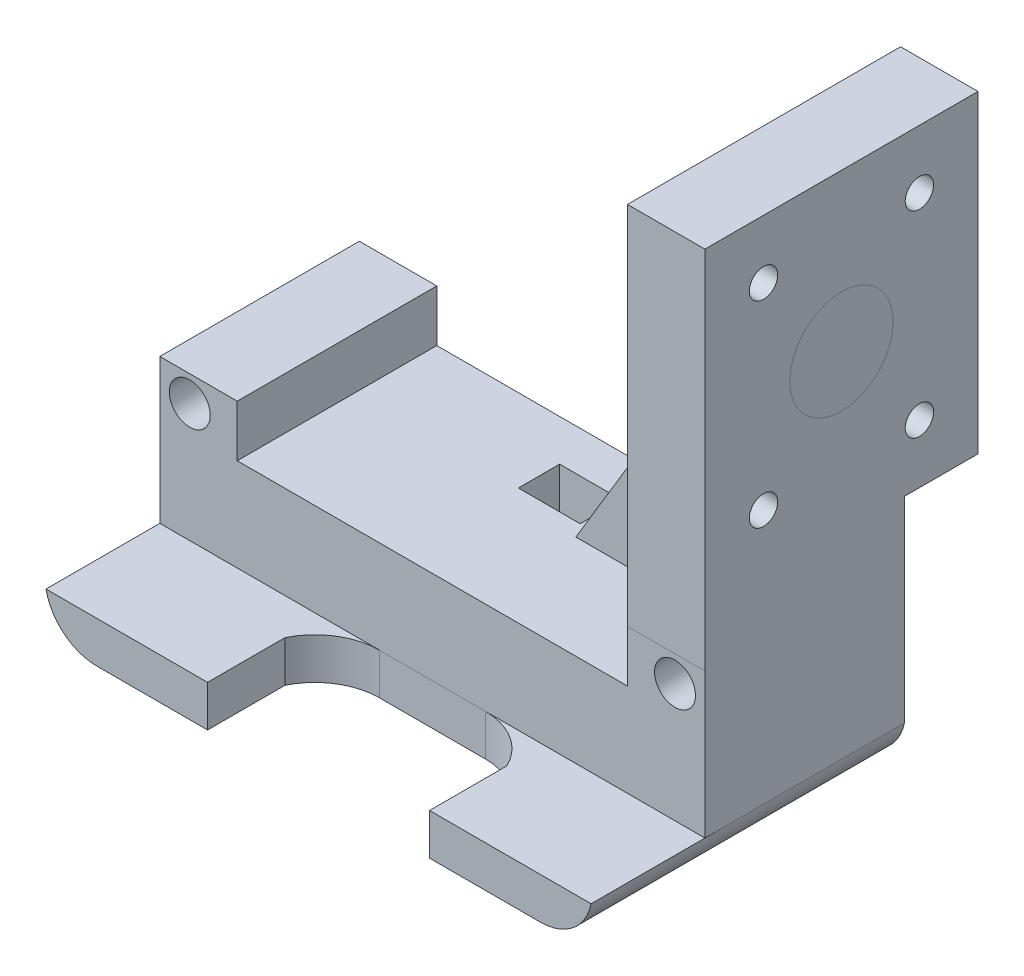
SolidWorks part; units mm, degrees
material "Custom Plastic"
ref_plane "Front Plane" through (0, 0, 0) normal (0, 0, 1) x (1, 0, 0)
ref_plane "Top Plane" through (0, 0, 0) normal (0, 1, 0) x (1, 0, 0)
ref_plane "Right Plane" through (0, 0, 0) normal (1, 0, 0) x (0, 0, -1)
sketch "Sketch2" plane through (0, 0, 0) normal (0, 1, 0) x (1, 0, 0)
  line L1 (-45, -15) -> (45, -15)
  line L2 (-45, -15) -> (-45, 15)
  line L3 (-45, 15) -> (45, 15)
  line L4 (45, -15) -> (45, 15)
  dimension "D1" = 90
  dimension "D2" = 30
  dimension "D3" = 15
  dimension "D4" = 45
extrude "Boss-Extrude1" add sketch "Sketch2" along normal blind 184.15
shell "Shell1" thickness 8 removed face at (0, 92.075, 15) outward yes
fillet "Fillet1" radius 10 8 edges at (53, 192.15, -4) (-53, 192.15, -4) (53, -8, -4) (-53, -8, -4) (45, 184.15, 0) (-45, 184.15, 0) (-45, 0, 0) (45, 0, 0)
sketch "Sketch3" plane through (0, -8, 0) normal (0, -1, 0) x (1, 0, 0)
  line L4 (-43, 15) -> (43, 15) construction
  line L5 (-21.5, 15) -> (21.5, 15)
  line L6 (-10.2526, -7.0461) -> (10.2526, -7.0461)
  line L7 (-21.5, 0) -> (-21.5, 15)
  line L8 (0, 36.7224) -> (0, -40.113) construction
  line L9 (21.5, 0) -> (21.5, 15)
  arc A0 (-10.2526, -7.0461) -> (-21.5, 0) centre (-10.2526, 5.4539) cw
  arc A1 (10.2526, -7.0461) -> (21.5, 0) centre (10.2526, 5.4539) ccw
  point P11 (0, -7.0461)
  dimension "D1" = 20.5051
  dimension "D2" = 43
  dimension "D4" = 12.5
  dimension "D5" = 15
extrude "Cut-Extrude1" cut sketch "Sketch3" against normal blind 15
sketch "Sketch16" plane through (0, 0, -23) normal (0, 0, -1) x (-1, 0, 0)
  line L0 (-53, 182.15) -> (-53, 2)
  line L1 (-43, -8) -> (43, -8)
  line L2 (53, 2) -> (53, 182.15)
  line L3 (43, 192.15) -> (-43, 192.15)
  arc A0 (-53, 2) -> (-43, -8) centre (-43, 2) ccw
  arc A1 (43, -8) -> (53, 2) centre (43, 2) ccw
  arc A2 (53, 182.15) -> (43, 192.15) centre (43, 182.15) ccw
  arc A3 (-43, 192.15) -> (-53, 182.15) centre (-43, 182.15) ccw
extrude "Boss-Extrude3" add sketch "Sketch16" along normal blind 12.7
sketch "Sketch19" plane through (53, 0, 0) normal (1, 0, 0) x (0, 0, -1)
  line L1 (-15, 192.15) -> (35.7, 192.15)
  line L2 (-15, 192.15) -> (-15, 2)
  line L3 (-15, 2) -> (35.7, 2)
  line L4 (35.7, 192.15) -> (35.7, 2)
extrude "Cut-Extrude3" cut sketch "Sketch19" against normal blind 160
sketch "Sketch20" plane through (0, 0, -15) normal (0, 0, 1) x (1, 0, 0)
  line L4 (41, 2) -> (-41, 2)
  line L5 (-35, 0) -> (35, 0)
  line L6 (41, 2) -> (-41, 2)
  line L7 (-35, 0) -> (35, 0)
  arc A4 (-41, 2) -> (-35, 0) centre (-35, 10) ccw
  arc A5 (35, 0) -> (41, 2) centre (35, 10) ccw
  arc A6 (-41, 2) -> (-35, 0) centre (-35, 10) ccw
  arc A7 (35, 0) -> (41, 2) centre (35, 10) ccw
  dimension "D1" = 0
extrude "Cut-Extrude4" cut sketch "Sketch20" against normal through all
sketch "Sketch21" plane through (21.5, 0, 0) normal (-1, 0, 0) x (0, 0, 1)
  line L1 (15, 0) -> (-35.7, 0)
  line L2 (15, 0) -> (15, 2)
  line L3 (15, 2) -> (-35.7, 2)
  line L4 (-35.7, 0) -> (-35.7, 2)
extrude "Cut-Extrude5" cut sketch "Sketch21" against normal through all and the other way through all
sketch "Sketch22" plane through (0, 0, 0) normal (0, 1, 0) x (1, 0, 0)
  line L0 (52.798, -15) -> (52.798, 35.7) construction
  line L1 (-52.798, 35.7) -> (52.798, 35.7)
  line L2 (-52.798, 35.7) -> (-52.798, 7.0461)
  line L3 (-52.798, 7.0461) -> (52.798, 7.0461)
  line L4 (52.798, 35.7) -> (52.798, 7.0461)
  dimension "D1" = 28.6539
extrude "Boss-Extrude4" add sketch "Sketch22" along normal blind 18
sketch "Sketch25" plane through (0, 18, 0) normal (0, 1, 0) x (1, 0, 0)
  line L0 (52.798, 35.7) -> (-52.798, 35.7) construction
  line L1 (-6, 35.7) -> (6, 35.7)
  line L2 (-6, 35.7) -> (-6, 29.7)
  line L3 (-6, 29.7) -> (6, 29.7)
  line L4 (6, 35.7) -> (6, 29.7)
  dimension "D1" = 6
  dimension "D2" = 6
  dimension "D3" = 12
extrude "Cut-Extrude7" cut sketch "Sketch25" against normal through all
sketch "Sketch26" plane through (0, 0, -35.7) normal (0, 0, -1) x (-1, 0, 0)
  line L8 (6, 18) -> (6, -8)
  line L9 (6, -8) -> (43, -8)
  line L10 (52.798, 0) -> (52.798, 18)
  line L11 (52.798, 18) -> (6, 18)
  line L12 (6, 18) -> (6, -8)
  line L13 (6, -8) -> (43, -8)
  line L14 (52.798, 0) -> (52.798, 18)
  line L15 (52.798, 18) -> (6, 18)
  line L20 (-6, -8) -> (-6, 18)
  line L21 (-6, 18) -> (-52.798, 18)
  line L22 (-52.798, 18) -> (-52.798, 0)
  line L23 (-43, -8) -> (-6, -8)
  line L24 (-6, -8) -> (-6, 18)
  line L25 (-6, 18) -> (-52.798, 18)
  line L26 (-52.798, 18) -> (-52.798, 0)
  line L27 (-43, -8) -> (-6, -8)
  arc A2 (43, -8) -> (52.798, 0) centre (43, 2) ccw
  arc A3 (43, -8) -> (52.798, 0) centre (43, 2) ccw
  arc A5 (-52.798, 0) -> (-43, -8) centre (-43, 2) ccw
  arc A6 (-52.798, 0) -> (-43, -8) centre (-43, 2) ccw
  dimension "D1" = 0
  dimension "D2" = 0
extrude "Boss-Extrude6" add sketch "Sketch26" along normal blind 10
sketch "Sketch27" plane through (0, -8, 0) normal (0, -1, 0) x (1, 0, 0)
  line L0 (6, -29.7) -> (6, -45.7) construction
  line L1 (-6, -29.7) -> (6, -29.7)
  line L2 (-6, -29.7) -> (-6, -37.7)
  line L3 (-6, -37.7) -> (6, -37.7)
  line L4 (6, -29.7) -> (6, -37.7)
  line L6 (-6, -37.7) -> (6, -37.7)
  line L7 (-6, -37.7) -> (-6, -45.7)
  line L8 (-6, -45.7) -> (6, -45.7)
  line L9 (6, -37.7) -> (6, -45.7)
  line M5 (-6, -45.7) -> (-6, -29.7)
  line M7 (6, -29.7) -> (6, -45.7)
  dimension "D1" = 8
extrude "Boss-Extrude7" add sketch "Sketch27" against normal up to surface (26 mm away) contours L8 L3 M5 M7 region at (0, -8, -41.7) up to face at (0, 18, -32.0365)
sketch "Sketch31" plane through (0, 18, 0) normal (0, 1, 0) x (1, 0, 0)
  line L0 (-52.798, 7.0461) -> (52.798, 7.0461) construction
  line L1 (-52.798, 45.7) -> (-37.798, 45.7)
  line L2 (-52.798, 45.7) -> (-52.798, 7.0461)
  line L3 (-52.798, 7.0461) -> (-37.798, 7.0461)
  line L4 (-37.798, 45.7) -> (-37.798, 7.0461)
  line L5 (0, -14.3) -> (0, 14.3) construction
  line L6 (52.798, 7.0461) -> (37.798, 7.0461)
  line L7 (37.798, 45.7) -> (37.798, 7.0461)
  line L8 (52.798, 45.7) -> (37.798, 45.7)
  line L9 (52.798, 45.7) -> (52.798, 7.0461)
  dimension "D1" = 15
extrude "Boss-Extrude8" add sketch "Sketch31" along normal blind 10
sketch "Sketch34" plane through (0, 0, -7.0461) normal (0, 0, 1) x (1, 0, 0)
  point P0 (-47, 23)
  point P2 (47, 23)
  dimension "D1" = 47
  dimension "D2" = 47
  dimension "D3" = 23
  dimension "D4" = 23
hole_wizard "5/16 (0.3125) Diameter Hole2" positions "Sketch34" profile "Sketch33" hole size "5/16" standard "ANSI Inch" end condition through all
sketch "Sketch33" plane through (-47, 23, -7.0461) normal (1, 0, 0) x (0, -1, 0)
  line L0 (0, 0) -> (0, 38.6539)
  line L1 (0, 38.6539) -> (3.9687, 38.6539)
  line L2 (3.9687, 38.6539) -> (3.9687, 0)
  line L5 (3.9687, 0) -> (0, 0)
  line L11 (0, -6.35) -> (0, 107.95) construction
  dimension "Thru Hole Dia." = 7.9375
  dimension "Thru Hole Depth" = 38.6539
sketch "Sketch35" plane through (52.798, 0, 0) normal (1, 0, 0) x (0, 0, -1)
  line L1 (7.0461, 28) -> (59.9461, 28)
  line L2 (7.0461, 28) -> (7.0461, 98.8)
  line L3 (7.0461, 98.8) -> (59.9461, 98.8)
  line L4 (59.9461, 28) -> (59.9461, 98.8)
  dimension "D1" = 70.8
  dimension "D2" = 52.9
extrude "Boss-Extrude9" add sketch "Sketch35" against normal up to surface (15 mm away) up to face at (37.798, 23, -26.3731)
sketch "Sketch38" plane through (52.798, 0, 0) normal (1, 0, 0) x (0, 0, -1)
  line L1 (7.0461, 98.8) -> (7.0461, 0) construction
  line L2 (59.9461, 28) -> (59.9461, 98.8) construction
  line L3 (59.9461, 98.8) -> (7.0461, 98.8) construction
  point P0 (48.5961, 87.45)
  point P2 (18.3961, 87.45)
  point P4 (18.3961, 49.35)
  point P6 (48.5961, 49.35)
  dimension "D1" = 30.2
  dimension "D2" = 38.1
  dimension "D3" = 30.2
  dimension "D4" = 38.1
  dimension "D5" = 11.35
  dimension "D6" = 11.35
  dimension "D7" = 11.35
  dimension "D8" = 11.35
hole_wizard "Ø5.5 (5.5) Diameter Hole1" positions "Sketch38" profile "Sketch37" hole size "Ø5.5" standard "ANSI Metric" end condition through all
sketch "Sketch37" plane through (52.798, 87.45, -48.5961) normal (0, 1, 0) x (0, 0, -1)
  line L0 (0, 0) -> (0, 105.5959)
  line L1 (0, 105.5959) -> (2.75, 105.5959)
  line L2 (2.75, 105.5959) -> (2.75, 0)
  line L5 (2.75, 0) -> (0, 0)
  line L11 (0, -6.35) -> (0, 107.95) construction
  dimension "Thru Hole Dia." = 5.5
  dimension "Thru Hole Depth" = 105.5959
sketch "Sketch39" plane through (0, 0, -7.0461) normal (0, 0, 1) x (1, 0, 0)
  line L0 (7.798, 18) -> (37.798, 18)
  line L1 (-37.798, 18) -> (37.798, 18) construction
  line L2 (37.798, 18) -> (37.798, 68)
  line L3 (37.798, 98.8) -> (37.798, 18) construction
  line L4 (37.798, 68) -> (7.798, 18)
  dimension "D1" = 30
  dimension "D2" = 50
extrude "Boss-Extrude10" add sketch "Sketch39" against normal up to surface (38.6539 mm away) up to face at (-43.0313, 23, -45.7)
sketch "Sketch40" plane through (0, 0, -7.0461) normal (0, 0, 1) x (1, 0, 0)
  line L13 (37.798, 68) -> (7.798, 18)
  line L14 (7.798, 18) -> (37.798, 18)
  line L15 (37.798, 18) -> (37.798, 68)
extrude "Cut-Extrude8" cut sketch "Sketch40" against normal blind 20
sketch "Sketch42" plane through (0, 0, -45.7) normal (0, 0, -1) x (-1, 0, 0)
  line L5 (-37.798, 68) -> (-7.798, 18)
  line L6 (-7.798, 18) -> (-37.798, 18)
  line L7 (-37.798, 18) -> (-37.798, 68)
extrude "Cut-Extrude10" cut sketch "Sketch42" against normal blind 2
sketch "Sketch43" plane through (52.798, 0, 0) normal (1, 0, 0) x (0, 0, -1)
  line L1 (59.9461, 28) -> (45.7, 28)
  line L2 (59.9461, 28) -> (59.9461, 38)
  line L3 (59.9461, 38) -> (45.7, 38)
  line L4 (45.7, 28) -> (45.7, 38)
  dimension "D1" = 10
  dimension "D2" = 14.2461
extrude "Cut-Extrude11" cut sketch "Sketch43" against normal through all
sketch "Sketch44" plane through (0, 0, -7.0461) normal (0, 0, 1) x (1, 0, 0)
  line L0 (-52.798, 28) -> (-37.798, 28)
  line L2 (-52.798, 28) -> (-52.798, 0)
  line L3 (-52.798, 0) -> (52.798, 0)
  line L4 (52.798, 28) -> (52.798, 0)
  line L5 (-37.798, 28) -> (-37.798, 18)
  line L6 (-37.798, 18) -> (37.798, 18)
  line L7 (37.798, 18) -> (37.798, 28)
  line L8 (37.798, 98.8) -> (37.798, 18) construction
  line L9 (37.798, 28) -> (52.798, 28)
split line "Split Line1"
sketch "Sketch45" plane through (52.798, 0, 0) normal (1, 0, 0) x (0, 0, -1)
  circle A0 centre (33.4961, 68.4) radius 10
  circle A1 centre (18.3961, 87.45) radius 2.75 construction
  point P6 (0, 0)
  dimension "D1" = 15.1
  dimension "D2" = 19.05
split line "Split Line2"
